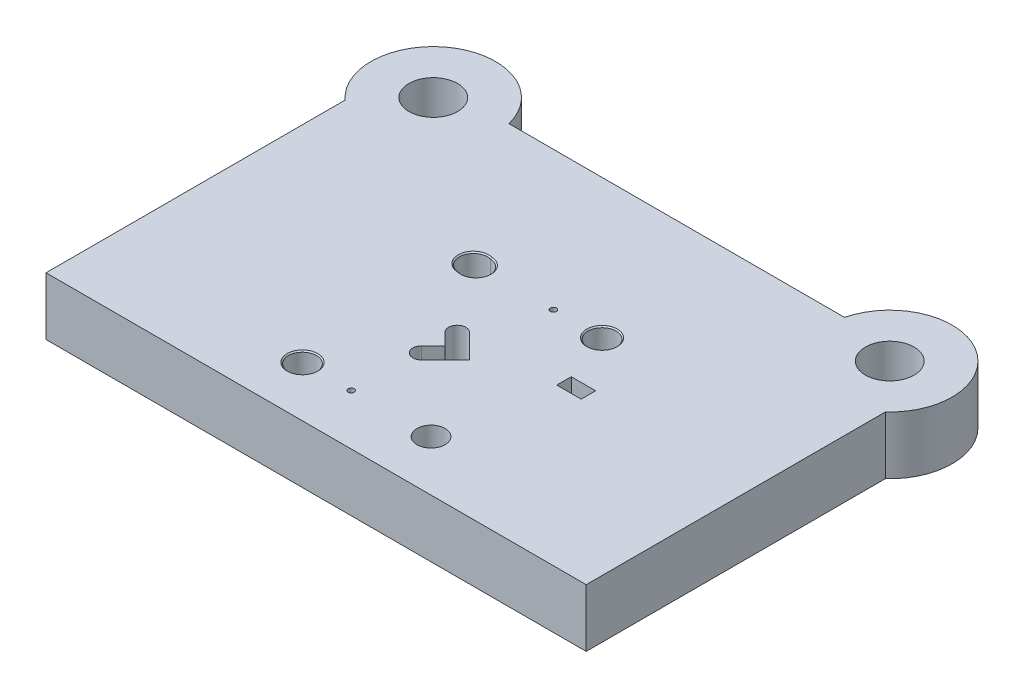
SolidWorks part; units mm, degrees
ref_plane "Front Plane" through (0, 0, 0) normal (0, 0, 1) x (1, 0, 0)
ref_plane "Top Plane" through (0, 0, 0) normal (0, 1, 0) x (1, 0, 0)
ref_plane "Right Plane" through (0, 0, 0) normal (1, 0, 0) x (0, 0, -1)
sketch "Sketch1" plane through (0, 0, 0) normal (0, 1, 0) x (1, 0, 0)
  line L0 (177.5, 0) -> (-177.5, 0)
  line L1 (-177.5, 0) -> (-177.5, 196.5903)
  line L2 (0, 0) -> (0, 237) construction
  line L3 (110.2382, 237) -> (-110.2382, 237)
  line L4 (177.5, 0) -> (177.5, 196.5903)
  arc A0 (-110.2382, 237) -> (-177.5, 196.5903) centre (-150, 227) ccw
  circle A1 centre (-150, 227) radius 16
  arc A2 (110.2382, 237) -> (177.5, 196.5903) centre (150, 227) cw
  circle A3 centre (150, 227) radius 16
  dimension "D3" = 82
  dimension "D4" = 32
  dimension "D1" = 227
  dimension "D2" = 237
  dimension "D5" = 355
  dimension "D6" = 300
extrude "Boss-Extrude1" add sketch "Sketch1" along normal blind 38
sketch "Sketch2" plane through (0, 0, 0) normal (0, -1, 0) x (1, 0, 0)
  line L8 (-4.8128, -89.5183) -> (-12.5344, -97.2399)
  line L9 (-4.8128, -89.5183) -> (-12.5344, -97.2399)
  line L10 (-4.5017, -105.2726) -> (11.2526, -89.5183)
  line L11 (-4.5017, -105.2726) -> (11.2526, -89.5183)
  line L12 (11.2526, -89.5183) -> (-4.5017, -73.7639)
  line L17 (11.2526, -89.5183) -> (-4.5017, -73.7639)
  line L18 (-12.5344, -81.7967) -> (-4.8128, -89.5183)
  line L19 (-12.5344, -81.7967) -> (-4.8128, -89.5183)
  line L30 (54.25, -113.43) -> (70.25, -113.43)
  line L31 (54.25, -103.93) -> (54.25, -113.43)
  line L32 (70.25, -103.93) -> (54.25, -103.93)
  line L33 (70.25, -113.43) -> (70.25, -103.93)
  line L34 (54.25, -113.43) -> (70.25, -113.43)
  line L35 (54.25, -103.93) -> (54.25, -113.43)
  line L36 (70.25, -103.93) -> (54.25, -103.93)
  line L37 (70.25, -113.43) -> (70.25, -103.93)
  circle A3 centre (42.25, -33.3) radius 5
  circle A4 centre (-42.25, -33.3) radius 5
  circle A5 centre (42.25, -145.68) radius 5
  arc A6 (-12.5344, -97.2399) -> (-4.5017, -105.2726) centre (-8.5181, -101.2563) ccw
  arc A7 (-12.5344, -97.2399) -> (-4.5017, -105.2726) centre (-8.5181, -101.2563) ccw
  circle A10 centre (-42.25, -145.68) radius 5
  circle A11 centre (10.25, -145.68) radius 1.99 construction
  circle A12 centre (-10.25, -33.3) radius 1.99 construction
  circle A13 centre (10.25, -145.68) radius 1.99
  circle A14 centre (-10.25, -33.3) radius 1.99
  arc A18 (-4.5017, -73.7639) -> (-12.5344, -81.7967) centre (-8.5181, -77.7803) ccw
  arc A19 (-4.5017, -73.7639) -> (-12.5344, -81.7967) centre (-8.5181, -77.7803) ccw
  dimension "D3" = 10
  dimension "D4" = 10
  dimension "D5" = 10
  dimension "D6" = 10
  dimension "D1" = 3
  dimension "D2" = 3
extrude "Cut-Extrude1" cut sketch "Sketch2" against normal through all
hole_wizard "M20x1.5 Tapped Hole1" positions "Sketch3" profile "Sketch4" tap size "M20x1.5" standard "DIN" end condition through all
sketch "Sketch3" plane through (0, 0, 0) normal (0, -1, 0) x (-1, 0, 0)
  point P0 (42.25, 33.3)
  point P3 (-42.25, 33.3)
  point P6 (-42.25, 145.68)
  point P9 (42.25, 145.68)
cosmetic thread "Hole Thread1" parameters "D2"=20
cosmetic thread "Hole Thread2" parameters "D2"=20
cosmetic thread "Hole Thread3" parameters "D2"=20
cosmetic thread "Hole Thread4" parameters "D2"=20
sketch "Sketch4" plane through (-42.25, 0, -33.3) normal (1, 0, 0) x (0, 0, -1)
  line L0 (0, 0) -> (0, 38)
  line L1 (0, 38) -> (9.25, 38)
  line L2 (9.25, 38) -> (9.25, 0)
  line L5 (9.25, 0) -> (0, 0)
  line L11 (0, -6.35) -> (0, 107.95) construction
  dimension "Thru Tap Drill Dia." = 18.5
  dimension "Thru Tap Drill Depth" = 38
hole_wizard "M20x1.5 Tapped Hole6" positions "Sketch14" profile "Sketch15" tap size "M20x1.5" standard "DIN" end condition through all
sketch "Sketch14" plane through (0, 38, 0) normal (0, 1, 0) x (1, 0, 0)
  point P0 (-40.4399, 145.4066)
sketch "Sketch15" plane through (-40.4399, 38, -145.4066) normal (1, 0, 0) x (0, 0, 1)
  line L0 (0, 0) -> (0, 38)
  line L1 (0, 38) -> (9.25, 38)
  line L2 (9.25, 38) -> (9.25, 0.775)
  line L3 (9.25, 0.775) -> (10.025, 0)
  line L5 (10.025, 0) -> (0, 0)
  line L6 (-9.25, 0.775) -> (-10.025, 0) construction
  line L11 (0, -6.35) -> (0, 107.95) construction
  dimension "Thru Tap Drill Dia." = 18.5
  dimension "Thru Tap Drill Depth" = 38
  dimension "Near C'Sink Dia." = 20.05
  dimension "Near C'Sink Angle" = 90
cosmetic thread "Hole Thread5" parameters "D2"=20
hole_wizard "M20x1.5 Tapped Hole7" positions "Sketch17" profile "Sketch18" tap size "M20x1.5" standard "DIN" end condition through all
sketch "Sketch17" plane through (0, 38, 0) normal (0, 1, 0) x (1, 0, 0)
  point P0 (42.25, 145.68)
  point P3 (-42.25, 145.68)
  point P5 (-42.25, 33.3)
sketch "Sketch18" plane through (42.25, 38, -145.68) normal (1, 0, 0) x (0, 0, 1)
  line L0 (0, 0) -> (0, 38)
  line L1 (0, 38) -> (9.25, 38)
  line L2 (9.25, 38) -> (9.25, 0.775)
  line L3 (9.25, 0.775) -> (10.025, 0)
  line L5 (10.025, 0) -> (0, 0)
  line L6 (-9.25, 0.775) -> (-10.025, 0) construction
  line L11 (0, -6.35) -> (0, 107.95) construction
  dimension "Thru Tap Drill Dia." = 18.5
  dimension "Thru Tap Drill Depth" = 38
  dimension "Near C'Sink Dia." = 20.05
  dimension "Near C'Sink Angle" = 90
cosmetic thread "Hole Thread6" parameters "D2"=20
cosmetic thread "Hole Thread7" parameters "D2"=20
cosmetic thread "Hole Thread8" parameters "D2"=20
